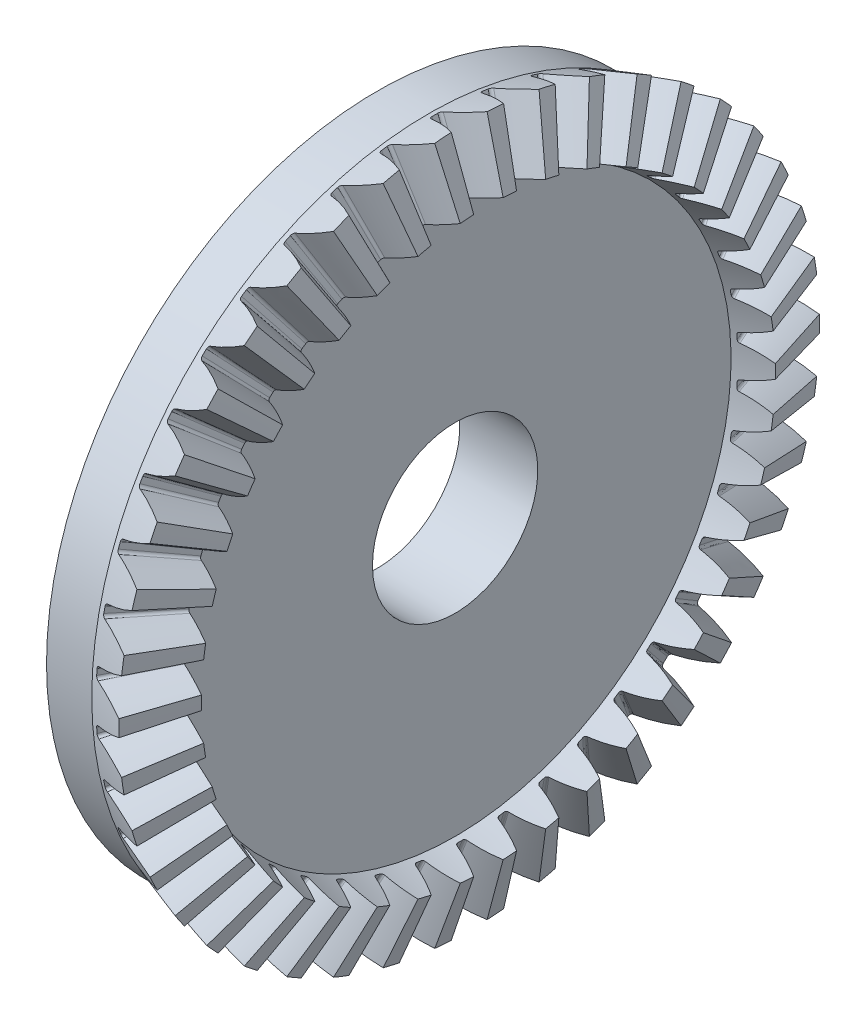
SolidWorks part; units mm, degrees
revolve "Base-Revolve" add sketch "BasProSke" angle 360 about L0 other way angle 4.286
sketch "BasProSke" plane through (0, 0, 0) normal (0, 1, 0) x (1, 0, 0)
  line L0 (-10, 0) -> (60, 0) construction
  line L1 (0, 0) -> (0, 10.184)
  line L2 (0, 0) -> (0.8038, 0)
  line L3 (0.8038, 0) -> (0.8038, 8.3437)
  line L4 (4.448, 0) -> (-9.0794, 40.5823) construction
  line L5 (0, 10.184) -> (1.2284, 10.5935)
  line L6 (4.448, 0) -> (-23.784, 92.8916) construction
  line L7 (4.448, 0) -> (0, 10.184) construction
  line L8 (1.2284, 10.5935) -> (1.8102, 8.6792)
  line L9 (1.8102, 8.6792) -> (0.8038, 8.3437)
  line L10 (0.948, 10.5) -> (-11.0363, 10.5) construction
  dimension "D1" = 20.368
  dimension "D2" = 4.448
  dimension "D3" = 11.068
  dimension "D4" = 1.53
ref_plane "Plane1" through (0, 0, 0) normal (0, 0, 1) x (1, 0, 0)
ref_plane "Plane2" through (0, 0, 0) normal (0, 1, 0) x (1, 0, 0)
ref_plane "Plane3" through (0, 0, 0) normal (1, 0, 0) x (0, 0, -1)
other "Configuration Table"
sketch "HoldingSke" plane through (0, 0, 0) normal (0, 1, 0) x (1, 0, 0)
  line L0 (0, 0) -> (1.4863, -1.3383)
  line L1 (-15, 0) -> (100, 0) construction
  line L2 (0, 0) -> (-121.1902, 29.4672)
  line L3 (0, 0) -> (-11.863, 4.5341)
  line L4 (0, 0) -> (6.4178, 5.7786)
  line L5 (0, 0) -> (-5.6217, -2.0967)
  line L6 (0, 0) -> (-10.5278, -7.1032)
  line L7 (-121.1902, 29.4672) -> (-120.9357, 35.4618)
  line L8 (-76.2, 0.5) -> (-75.3, 0.5)
  line L9 (-71.009, 38.7566) -> (-53.1078, 45.2721)
  line L10 (-76.2, 71.12) -> (104.1128, 71.12)
  line L11 (0, 0) -> (-2, 0)
  line L12 (-76.2, 101.6) -> (-76.181, 101.6)
  line L13 (24.9733, 27.94) -> (52.9546, 28.2287)
  line L14 (24.9733, 27.94) -> (24.9743, 27.94)
  line L15 (24.9733, 27.94) -> (100.3893, 30.0425)
  line L16 (-121.1902, 29.4672) -> (4.0821, -1.7667)
  circle A0 centre (0, 0) radius 2.5
  circle A1 centre (0, 0) radius 10
  circle A2 centre (0, 0) radius 10
  circle A3 centre (0, 0) radius 2.5
  dimension "Num_teeth" = 42
  dimension "Pitch_radius" = 180.3128
  dimension "Width" = 2
ref_plane "ToothPln" through (0.6142, 10.3887, 0) normal (-0.3162, 0.9487, 0) x (0, 0, -1)
ref_plane "ToothPln2" through (0.4448, -1.3344, 0) normal (-0.3162, 0.9487, 0) x (0, 0, 1)
sketch "TooCutSke" plane through (0.6142, 10.3887, 0) normal (-0.3162, 0.9487, 0) x (0, 0, -1)
  line L2 (0, 10.1481) -> (123.6488, -1639.8299) construction
  line L3 (0, 10.1481) -> (67.6834, -1755.935) construction
  line L4 (0, -15.621) -> (0, 105.791) construction
  line L6 (-24.765, -0.6474) -> (21.082, -0.6474) construction
  line L7 (0.7847, -0.3225) -> (0.4018, -0.3372) construction
  arc A0 (-0.6515, -0.8441) -> (0.6515, -0.8441) centre (0, 10.1481) ccw
  arc A1 (-0.0871, 0.448) -> (0.0871, 0.448) centre (0, 10.1481) ccw
  circle A2 centre (0, 10.1481) radius 10.5 construction
  circle A3 centre (0, 10.1481) radius 9.8668 construction
  arc A4 (0.1809, 0.373) -> (0.0871, 0.448) centre (0.088, 0.353) ccw
  arc A5 (0.1809, 0.373) -> (0.6515, -0.8441) centre (4.2859, 1.2608) ccw
  arc A6 (-0.6515, -0.8441) -> (-0.1809, 0.373) centre (-4.2859, 1.2608) ccw
  arc A7 (-0.0871, 0.448) -> (-0.1809, 0.373) centre (-0.088, 0.353) ccw
  ellipse E0 centre (0, 2.7025) end of major axis (10.5935, 2.7025) minor radius 3.3499 construction
sketch "TooCutSke2" plane through (0.4448, -1.3344, 0) normal (-0.3162, 0.9487, 0) x (0, 0, 1)
  line L0 (0, 0) -> (0, 68.072) construction
  line L2 (21.082, 3.2205) -> (-20.32, 3.2205) construction
  circle A0 centre (0, 4.2198) radius 0.0127
  ellipse E1 centre (0, 0) end of major axis (-10.184, 0) minor radius 3.2205 construction
loft "ToothCut" cut profiles "TooCutSke2", "TooCutSke"
pattern_circular "TeethCuts" count 42 every 8.571 about axis through (-10, 0, 0) along (1, 0, 0) of "ToothCut"
sketch "HubSke" plane through (0, 0, 0) normal (-1, 0, 0) x (0, 0, 1)
  circle A0 centre (0, 0) radius 10
  dimension "Diameter" = 20
extrude "Hub" add sketch "HubSke" along normal blind 1.5521
sketch "BorSke" plane through (0, 0, 0) normal (1, 0, 0) x (0, 0, -1)
  circle A0 centre (0, 0) radius 2.5
  dimension "Diameter" = 5
extrude "Bore" cut sketch "BorSke" along normal mid plane 12.0001
sketch "KeySke" plane through (0, 0, 0) normal (1, 0, 0) x (0, 0, -1)
  line L0 (-1, 0) -> (-1, 3.4)
  line L1 (-1, 3.4) -> (1, 3.4)
  line L2 (1, 3.4) -> (1, 0)
  line L3 (0, 0) -> (0, 34) construction
  line L4 (-1, 0) -> (1, 0)
  dimension "Width" = 2
  dimension "Offset" = 3.4
extrude "Keyway" [suppressed] cut sketch "KeySke" along normal mid plane 12.0001
pattern_circular "Keyway2" [suppressed] count 2 every 90 about axis through (-10, 0, 0) along (1, 0, 0) reverse direction yes
equation "' \"Module@HoldingSke\" = 6.35"
equation "' \"Num_teeth@HoldingSke\" = 20"
equation "' \"Mating_teeth@HoldingSke\" = 12"
equation "' \"Ap@HoldingSke\" =  20"
equation "' \"Ap@HoldingSke\" = 20"
equation "' \"Width@HoldingSke\" = 0.5 * 25.4"
equation "' \"Hub_dia@HoldingSke\"= 2 * 25.4"
equation "' \"Hub_dia@HoldingSke\" = 2 * 25.4"
equation "' \"Mounting_dist@HoldingSke\" = 3 * 25.4"
equation "' \"Bore@HoldingSke\" = 19"
equation "' \"T_dim@HoldingSke\" = 0.1 * 25.4"
equation "' \"Width@KeySke\" = 0.25 * 25.4"
equation "' \"Show_teeth@HoldingSke\" = 100"
equation "' \"Backlash@HoldingSke\" = 0.009 * 25.4"
equation "' \"Addendum_fac@HoldingSke\" = 1.0"
equation "' \"Dedendum_fac@HoldingSke\" = 1.188"
equation "' \"Dedendum_add@HoldingSke\" = 0.002 * 25.4"
equation "' \"Clearance_fac@HoldingSke\" = 0.188"
equation "\"Pitch@HoldingSke\" = 1 / \"Module@HoldingSke\""
equation " \"Addendum_fac@HoldingSke\" = 0.54 + 0.46 / (\"Num_teeth@HoldingSke\" /  \"Mating_teeth@HoldingSke\" ) ^ 2"
equation "' \"Addendum_fac@HoldingSke\" = 2 - (0.54 + 0.46 / (\"Mating_teeth@HoldingSke\" /  \"Num_teeth@HoldingSke\" ) ^ 2)"
equation "\"Dedendum_fac@HoldingSke\" = 2.188 - \"Addendum_fac@HoldingSke\""
equation "\"Pitch_rad@BasProSke\" = \"Num_teeth@HoldingSke\" / \"Pitch@HoldingSke\" / 2"
equation "\"Pitch_ang@BasProSke\" = atn(\"Num_teeth@HoldingSke\" / \"Mating_teeth@HoldingSke\") * (180 / 3.14159265)"
equation "\"Addendum@BasProSke\" = \"Addendum_fac@HoldingSke\" / \"Pitch@HoldingSke\""
equation "\"Dedendum_plus@BasProSke\" = (\"Dedendum_fac@HoldingSke\" / \"Pitch@HoldingSke\" + \"Dedendum_add@HoldingSke\") * 1.25"
equation "\"Face_wid@BasProSke\" = \"Width@HoldingSke\""
equation "\"Radius@TooCutSke\" = ((\"Num_teeth@HoldingSke\" + 2 * \"Addendum_fac@HoldingSke\") / \"Pitch@HoldingSke\" ) / 2"
equation "\"Overcut_dia@TooCutSke\" =  1.02 * (\"Num_teeth@HoldingSke\" + 2 * \"Addendum_fac@HoldingSke\") / \"Pitch@HoldingSke\""
equation "\"Pitch_dia@TooCutSke\" = \"Num_teeth@HoldingSke\" / \"Pitch@HoldingSke\""
equation "\"Base_dia@TooCutSke\" = \"Num_teeth@HoldingSke\" / \"Pitch@HoldingSke\" * cos((\"Ap@HoldingSke\"  * 3.14159265 / 180))"
equation "'  \"Root_dia@TooCutSke\" =  (\"Num_teeth@HoldingSke\" + 2) / \"Pitch@HoldingSke\" - 2 * (\"Addendum_fac@HoldingSke\" + \"Dedendum_fac@HoldingSke\") / \"Pitch@HoldingSke\" - \"Dedendum_add@HoldingSke\" * 2"
equation "'  \"Root_dia@TooCutSke\" = (\"Num_teeth@HoldingSke\" + 2) / \"Pitch@HoldingSke\" - 2 * (\"Addendum_fac@HoldingSke\" + \"Dedendum_fac@HoldingSke\") / \"Pitch@HoldingSke\" - \"Dedendum_add@HoldingSke\" * 2"
equation "\"Root_dia@TooCutSke\" =  \"Num_teeth@HoldingSke\" / \"Pitch@HoldingSke\" -  2 * \"Dedendum_fac@HoldingSke\" / \"Pitch@HoldingSke\" - \"Dedendum_add@HoldingSke\" * 2"
equation "\"Half_ang@TooCutSke\" = 180 / \"Num_teeth@HoldingSke\""
equation "\"Half_CT@TooCutSke\" = \"Num_teeth@HoldingSke\" / \"Pitch@HoldingSke\" * sin((3.14159265 / 2 / \"Num_teeth@HoldingSke\")) / 2 - 2 * \"Backlash@HoldingSke\" / 4"
equation "\"Flank_rad@TooCutSke\" = \"Num_teeth@HoldingSke\" / \"Pitch@HoldingSke\" / 5"
equation "\"Root_fillet@TooCutSke\" = \"Clearance_fac@HoldingSke\" / \"Pitch@HoldingSke\" + \"Dedendum_add@HoldingSke\""
equation "\"Offset@ToothPln2\"  = \"Num_teeth@HoldingSke\" / \"Pitch@HoldingSke\" / 2 / sin(atn(\"Num_teeth@HoldingSke\" / \"Mating_teeth@HoldingSke\"))"
equation "\"Dedendum_plus@TooCutSke2\" = \"Dedendum_plus@BasProSke\""
equation "\"MHD@HoldingSke\" = \"Num_teeth@HoldingSke\" / \"Pitch@HoldingSke\" - 2 * \"Dedendum_plus@BasProSke\" * cos(atn(\"Num_teeth@HoldingSke\" / \"Mating_teeth@HoldingSke\"))"
equation "\"MBD@HoldingSke\" = \"Num_teeth@HoldingSke\" / \"Pitch@HoldingSke\" - 2 * \"Dedendum_plus@BasProSke\" * cos(atn(\"Num_teeth@HoldingSke\" / \"Mating_teeth@HoldingSke\")) - 0.002 * 25.4"
equation "\"MnMD@HoldingSke\" =  \"Num_teeth@HoldingSke\" / \"Pitch@HoldingSke\" / 2 / (\"Num_teeth@HoldingSke\" / \"Mating_teeth@HoldingSke\") + \"Dedendum_plus@BasProSke\" * sin(atn(\"Num_teeth@HoldingSke\" / \"Mating_teeth@HoldingSke\"))"
equation "\"OAL@HoldingSke\" = \"MnMD@HoldingSke\""
equation "\"MHD@HoldingSke\" = ((sgn( \"MHD@HoldingSke\" - \"Hub_dia@HoldingSke\" )-1)*( \"MHD@HoldingSke\" - \"Hub_dia@HoldingSke\" ))/-2+ \"Hub_dia@HoldingSke\""
equation "\"MBD@HoldingSke\" = ((sgn( \"MBD@HoldingSke\" - \"Bore@HoldingSke\" )-1)*( \"MBD@HoldingSke\" - \"Bore@HoldingSke\" ))/-2+ \"Bore@HoldingSke\""
equation "\"Face_wid@BasProSke\" = ((sgn( \"Face_wid@BasProSke\" - \"Offset@ToothPln2\" * 0.9)-1)*( \"Face_wid@BasProSke\" - \"Offset@ToothPln2\" * 0.9))/-2+ \"Offset@ToothPln2\" * 0.9"
equation "\"OAL@HoldingSke\" = ((sgn( \"OAL@HoldingSke\" - \"Mounting_dist@HoldingSke\" )+1)*( \"OAL@HoldingSke\" - \"Mounting_dist@HoldingSke\" ))/2 + \"Mounting_dist@HoldingSke\" + 0.000002 * 25.4"
equation "\"Num_teeth@TeethCuts\" = int( \"Show_teeth@HoldingSke\" ) + 1"
equation "\"Num_teeth@TeethCuts\" = ((sgn( \"Num_teeth@TeethCuts\" - \"Num_teeth@HoldingSke\" )-1)*( \"Num_teeth@TeethCuts\" - \"Num_teeth@HoldingSke\" ))/-2+ \"Num_teeth@HoldingSke\""
equation "\"Num_teeth@TeethCuts\" = ((sgn( \"Num_teeth@TeethCuts\" - 2.0)+1)*( \"Num_teeth@TeethCuts\" - 2.0))/2 +2.0"
equation "\"Angle@TeethCuts\" = 360.0 / \"Num_teeth@HoldingSke\""
equation "\"Diameter@HubSke\" = \"MHD@HoldingSke\""
equation "\"Length@Hub\" = \"OAL@HoldingSke\" - \"MnMD@HoldingSke\" + 0.000002 * 25.4"
equation "\"Diameter@BorSke\" = \"MBD@HoldingSke\""
equation "\"D1@Bore\" = \"OAL@HoldingSke\" * 2.0"
equation "\"D1@Keyway\" = \"OAL@HoldingSke\" * 2.0"
equation "\"Offset@KeySke\" = \"T_dim@HoldingSke\" + \"MBD@HoldingSke\" / 2.0"
